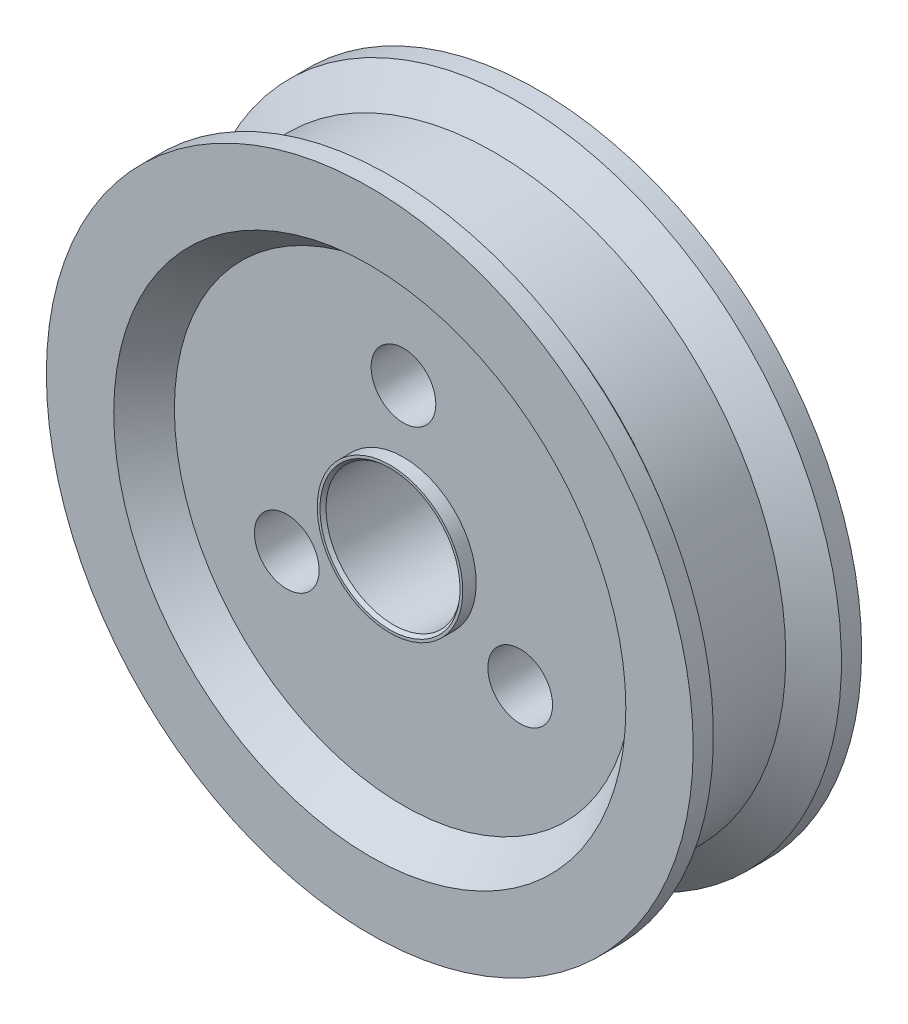
SolidWorks part; units mm, degrees
ref_plane "Plan de face" through (0, 0, 0) normal (0, 0, 1) x (1, 0, 0)
ref_plane "Plan de dessus" through (0, 0, 0) normal (0, 1, 0) x (1, 0, 0)
ref_plane "Plan de droite" through (0, 0, 0) normal (1, 0, 0) x (0, 0, -1)
sketch "Esquisse1" plane through (0, 0, 0) normal (0, 0, 1) x (1, 0, 0)
  circle A0 centre (0, 0) radius 60
  circle A1 centre (0, 0) radius 12.5
  dimension "D1" = 120
  dimension "D2" = 25
extrude "Boss.-Extru.1" add sketch "Esquisse1" along normal mid plane 25
sketch "Esquisse3" plane through (0, 0, 12.5) normal (0, 0, 1) x (1, 0, 0)
  line L0 (0, 0) -> (0, 12.5) construction
  circle A0 centre (0, 0) radius 12.5 construction
  circle A1 centre (0, 0) radius 42.5
  dimension "D1" = 85
extrude "Enlèv. mat.-Extru.1" cut sketch "Esquisse3" against normal mid plane 10
mirror "Symétrie1" about plane through (0, 0, 0) normal (0, 0, 1) of "Enlèv. mat.-Extru.1"
sketch "Esquisse4" plane through (0, 0, 7.5) normal (0, 0, 1) x (1, 0, 0)
  line L0 (0, 25) -> (0, 0) construction
  line L1 (0, 0) -> (-21.6506, -12.5) construction
  line L2 (0, 0) -> (21.6506, -12.5) construction
  circle A0 centre (0, 0) radius 25 construction
  circle A1 centre (0, 25) radius 6
  circle A2 centre (21.6506, -12.5) radius 6
  circle A3 centre (-21.6506, -12.5) radius 6
  point P12 (0, 0)
  dimension "D1" = 50
  dimension "D2" = 12
  dimension "D4" = 120
  dimension "D5" = 120
  dimension "D3" = 3
extrude "Enlèv. mat.-Extru.2" cut sketch "Esquisse4" against normal through all
sketch "Esquisse5" plane through (0, 0, 0) normal (0, 1, 0) x (1, 0, 0)
  line L0 (0, 12.5) -> (0, -12.5) construction
  line L1 (60, 12.5) -> (-60, 12.5) construction
  line L2 (-60, -12.5) -> (60, -12.5) construction
  line L3 (60, 9.5) -> (54, 6.0359)
  line L4 (60, -12.5) -> (60, 12.5) construction
  line L5 (54, 6.0359) -> (54, -6.0359)
  line L6 (54, -6.0359) -> (60, -9.5)
  line L7 (60, -9.5) -> (60, 9.5)
  dimension "D1" = 6
  dimension "D2" = 3
  dimension "D3" = 3
  dimension "D4" = 60
revolve "Enlèvement de matière-Révolution1" cut sketch "Esquisse5" angle 360 about L0
sketch "Esquisse6" plane through (0, 0, -7.5) normal (0, 0, -1) x (-1, 0, 0)
  circle A0 centre (0, 0) radius 12.5 construction
  circle A1 centre (0, 0) radius 12.5
  circle A2 centre (0, 0) radius 13.5
  dimension "D1" = 27
extrude "Boss.-Extru.2" add sketch "Esquisse6" along normal blind 2 and the other way blind 17
chamfer "Chanfrein1" distance 5 angle 45 2 edges at (42.5, 0, 12.5) (42.5, 0, -12.5)
chamfer "Chanfrein2" distance 0.5 angle 45 2 edges at (-12.5, 0, -9.5) (-12.5, 0, 9.5)
scale "Escala1" scale about origin uniform scaling yes scale factor 0.63332
scale "Escala2" scale about origin uniform scaling no x scale factor 1 y scale factor 1 z scale factor 1.249921
